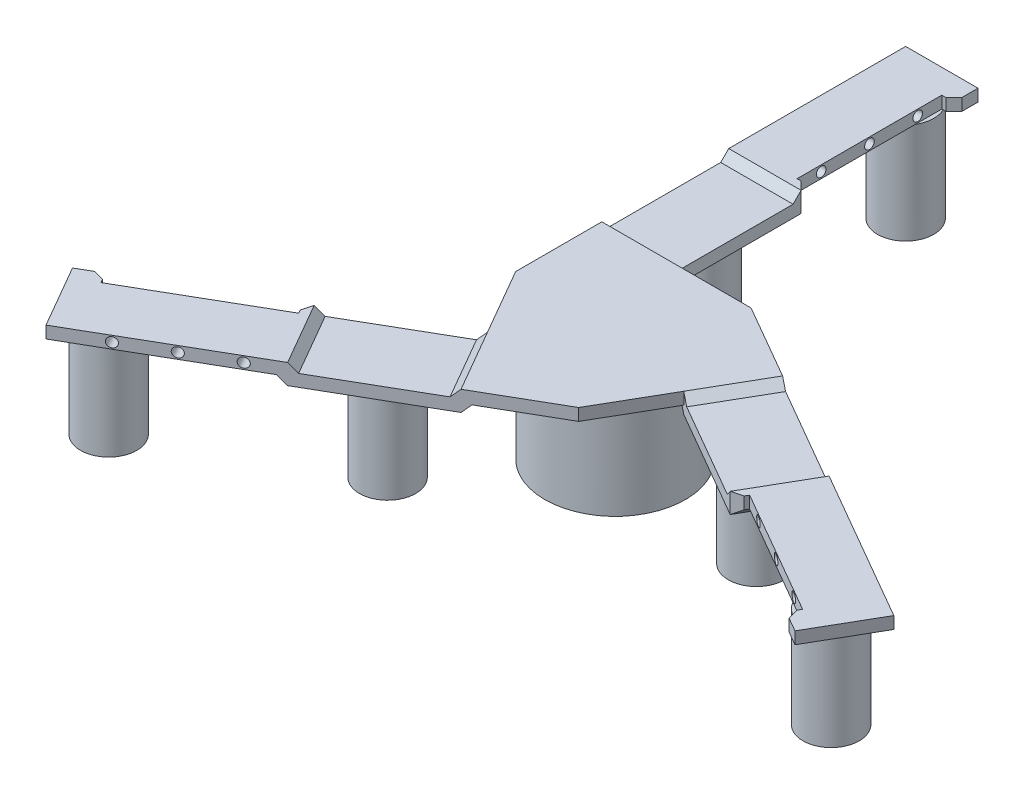
SolidWorks part; units mm, degrees
note: The reader was unsure of these and kept them because the rebuilt part matched: shared geometry of "Croquis11<5>".
ref_plane "Alzado" through (0, 0, 0) normal (0, 0, 1) x (1, 0, 0)
ref_plane "Planta" through (0, 0, 0) normal (0, 1, 0) x (1, 0, 0)
ref_plane "Vista lateral" through (0, 0, 0) normal (1, 0, 0) x (0, 0, -1)
sketch "Croquis1" plane through (0, 0, 0) normal (0, 1, 0) x (1, 0, 0)
  line L0 (0, 0) -> (0, 97) construction
  line L1 (0, 0) -> (84.0045, -48.5) construction
  line L2 (0, 0) -> (-84.0045, -48.5) construction
  line L3 (-24.75, 0) -> (-24.75, 97)
  line L4 (12.375, 21.4341) -> (96.3795, -27.0659)
  line L5 (12.375, -21.4341) -> (-71.6295, -69.9341)
  line L6 (-6.75, 21.4341) -> (-6.75, 97)
  line L7 (21.9375, -4.8714) -> (87.3795, -42.6543)
  line L8 (-15.1875, -16.5627) -> (-80.6295, -54.3457)
  line L9 (-71.6295, -69.9341) -> (-80.6295, -54.3457)
  line L10 (96.3795, -27.0659) -> (87.3795, -42.6543)
  line L11 (-6.75, 97) -> (-24.75, 97)
  line L15 (12.375, 21.4341) -> (-6.75, 21.4341)
  line L16 (-24.75, 0) -> (-15.1875, -16.5627)
  line L17 (12.375, -21.4341) -> (21.9375, -4.8714)
  line L18 (-6.75, 0) -> (-6.75, 97) construction
  line L19 (3.375, -5.8457) -> (-80.6295, -54.3457) construction
  line L20 (3.375, 5.8457) -> (87.3795, -42.6543) construction
  point P7 (0, 0)
  dimension "D1" = 97
  dimension "D3" = 24.75
  dimension "D4" = 24.75
  dimension "D5" = 24.75
  dimension "D6" = 18
  dimension "D7" = 18
  dimension "D8" = 18
  dimension "D2" = 3
extrude "Saliente-Extruir2" add sketch "Croquis1" along normal blind 1
sketch "Croquis2" plane through (0, 0, 0) normal (0, 1, 0) x (1, 0, 0)
  line L0 (-15.75, 97) -> (-15.75, 88) construction
  line L1 (-6.75, 97) -> (-24.75, 97) construction
  line L2 (91.8795, -34.8601) -> (84.0852, -30.3601) construction
  line L3 (-76.1295, -62.1399) -> (-68.3352, -57.6399) construction
  line L4 (-15.75, 88) -> (-15.75, 53) construction
  line L5 (-15.75, 53) -> (-15.75, 21.4341) construction
  circle A0 centre (0, 0) radius 17.5
  circle A1 centre (0, 0) radius 15.5
  circle A2 centre (-15.75, 88) radius 7
  circle A3 centre (-15.75, 88) radius 5
  circle A4 centre (84.0852, -30.3601) radius 7
  circle A5 centre (84.0852, -30.3601) radius 5
  circle A6 centre (-68.3352, -57.6399) radius 7
  circle A7 centre (-68.3352, -57.6399) radius 5
  circle A8 centre (-15.75, 37.2171) radius 7
  circle A10 centre (-15.75, 37.2171) radius 5
  circle A11 centre (40.1059, -4.9686) radius 7
  circle A12 centre (40.1059, -4.9686) radius 5
  circle A13 centre (-24.3559, -32.2484) radius 7
  circle A14 centre (-24.3559, -32.2484) radius 5
  point P13 (-15.75, 37.2171)
  point P25 (0, 0)
  point P42 (0, 0)
  dimension "D1" = 35
  dimension "D3" = 14
  dimension "D8" = 14
  dimension "D5" = 9
  dimension "D7" = 44
  dimension "D2" = 2
  dimension "D4" = 2
  dimension "D9" = 2
  dimension "D6" = 3
  dimension "D10" = 3
extrude "Saliente-Extruir3" add sketch "Croquis2" against normal blind 25
sketch "Croquis3" plane through (0, 0, 0) normal (0, 1, 0) x (1, 0, 0)
  line L0 (-6.75, 21.4341) -> (-6.75, 97) construction
  line L1 (-24.75, 97) -> (-6.75, 97)
  line L2 (-24.75, 97) -> (-24.75, 53)
  line L3 (-24.75, 53) -> (-6.75, 53)
  line L4 (-6.75, 97) -> (-6.75, 53)
  line L5 (96.3795, -27.0659) -> (58.2743, -5.0659)
  line L6 (96.3795, -27.0659) -> (87.3795, -42.6543)
  line L7 (87.3795, -42.6543) -> (49.2743, -20.6543)
  line L8 (58.2743, -5.0659) -> (49.2743, -20.6543)
  line L9 (-71.6295, -69.9341) -> (-33.5243, -47.9341)
  line L10 (-71.6295, -69.9341) -> (-80.6295, -54.3457)
  line L11 (-80.6295, -54.3457) -> (-42.5243, -32.3457)
  line L12 (-33.5243, -47.9341) -> (-42.5243, -32.3457)
  line L13 (-6.75, 21.4341) -> (-24.75, 21.4341)
  line L14 (-24.75, 97) -> (-24.75, 0) construction
  line L15 (-24.75, 21.4341) -> (-24.75, 0)
  line L16 (-24.75, 0) -> (-15.1875, -16.5627)
  line L17 (-15.1875, -16.5627) -> (-6.1875, -32.1512)
  line L18 (-71.6295, -69.9341) -> (12.375, -21.4341) construction
  line L19 (-6.1875, -32.1512) -> (12.375, -21.4341)
  line L20 (12.375, -21.4341) -> (21.9375, -4.8714)
  line L21 (21.9375, -4.8714) -> (30.9375, 10.7171)
  line L22 (96.3795, -27.0659) -> (12.375, 21.4341) construction
  line L23 (30.9375, 10.7171) -> (12.375, 21.4341)
  line L24 (12.375, 21.4341) -> (-6.75, 21.4341)
  point P17 (0, 0)
  dimension "D1" = 44
  dimension "D2" = 3
extrude "Saliente-Extruir4" add sketch "Croquis3" along normal blind 2 from surface at 1 starting at face at (0, 1, 0)
sketch "Croquis4" plane through (0, 0, 0) normal (0, 1, 0) x (1, 0, 0)
  line L0 (58.2743, -5.0659) -> (30.9375, 10.7171)
  line L1 (-24.75, 53) -> (-6.75, 53)
  line L2 (-24.75, 53) -> (-24.75, 21.4341)
  line L3 (-24.75, 21.4341) -> (-6.75, 21.4341)
  line L4 (-6.75, 53) -> (-6.75, 21.4341)
  line L5 (58.2743, -5.0659) -> (49.2743, -20.6543)
  line L6 (49.2743, -20.6543) -> (21.9375, -4.8714)
  line L7 (30.9375, 10.7171) -> (21.9375, -4.8714)
  line L8 (-33.5243, -47.9341) -> (-6.1875, -32.1512)
  line L9 (-33.5243, -47.9341) -> (-42.5243, -32.3457)
  line L10 (-42.5243, -32.3457) -> (-15.1875, -16.5627)
  line L11 (-6.1875, -32.1512) -> (-15.1875, -16.5627)
  point P16 (0, 0)
  dimension "D1" = 3
extrude "Saliente-Extruir5" add sketch "Croquis4" against normal blind 2
chamfer "Chaflán1" distance 2 angle 45 12 edges at (-38.0243, 1, 40.1399) (53.7743, 1, 12.8601) (-15.75, 1, -53) (-10.6875, 1, 24.357) (26.4375, 1, -2.9228) (-15.75, 1, -21.4341) (-15.75, 0, -21.4341) (-15.75, 0, -53) (26.4375, 0, -2.9228) (53.7743, 0, 12.8601) (-10.6875, 0, 24.357) (-38.0243, 0, 40.1399)
sketch "Croquis6" plane through (0, 0, 0) normal (1, 0, 0) x (0, 0, -1)
  line L0 (0, -1000) -> (0, 49000) construction
sketch "Croquis11" plane through (0, 0, 0) normal (1, 0, 0) x (0, 0, -1)
  line L0 (97, 1.5) -> (85, 1.5) construction
  line L1 (97, 3) -> (97, 0) construction
  line L2 (85, 1.5) -> (73, 1.5) construction
  line L3 (73, 1.5) -> (61, 1.5) construction
  line L9 (53, 3) -> (97, 3) construction
  line L10 (55, 0) -> (91, 0)
  line L11 (55, 0) -> (55, 3)
  line L16 (55, 3) -> (91, 3)
  line L17 (91, 0) -> (91, 3)
  line L22 (55, 0) -> (91, 3) construction
  line L23 (55, 3) -> (91, 0) construction
  circle A0 centre (61, 1.5) radius 1.2
  circle A1 centre (73, 1.5) radius 1.2
  circle A2 centre (85, 1.5) radius 1.2
  dimension "D4" = 2.4
  dimension "D5" = 2.4
  dimension "D6" = 2.4
  dimension "D1" = 12
  dimension "D2" = 12
  dimension "D3" = 12
extrude "Cortar-Extruir3" cut sketch "Croquis11" against normal up to next contours A0 | A1 | A2
extrude "Cortar-Extruir6" cut sketch "Croquis11<5>" against normal blind 9.75
sketch "Croquis11<5>" plane through (0, 0, 0) normal (1, 0, 0) x (0, 0, -1) same geometry as "Croquis11"
pattern_circular "MatrizC5" count 3 over 360 about axis through (0, 0, 0) along (0, 1, 0) of "Cortar-Extruir3", "Cortar-Extruir6"
chamfer "Chaflán4" distance 2 angle 45 9 edges at (-6.75, -1, -54) (50.1404, -1, 21.1543) (-43.3904, -1, 32.8457) (-6.75, 1.5, -91) (-6.75, 1.5, -55) (-75.4333, 1.5, 51.3457) (-44.2564, 1.5, 33.3457) (82.1833, 1.5, 39.6543) (51.0064, 1.5, 21.6543)
